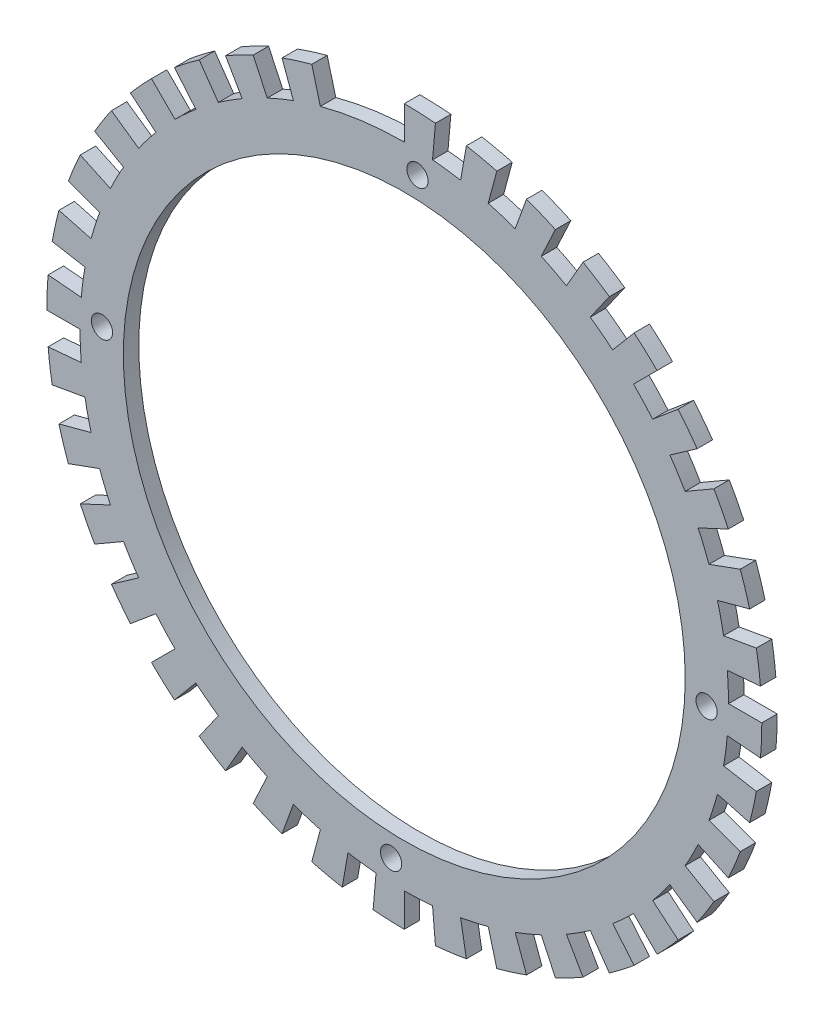
SolidWorks part; units mm, degrees
ref_plane "Front Plane" through (0, 0, 0) normal (0, 0, 1) x (1, 0, 0)
ref_plane "Top Plane" through (0, 0, 0) normal (0, 1, 0) x (1, 0, 0)
ref_plane "Right Plane" through (0, 0, 0) normal (1, 0, 0) x (0, 0, -1)
sketch "Sketch1" plane through (0, 0, 0) normal (0, 0, 1) x (1, 0, 0)
  line L0 (0, 82.7) -> (0, 75)
  line L1 (7.2078, 82.3853) -> (6.5367, 74.7146)
  line L2 (0, 75) -> (0, 0) construction
  line L3 (6.5367, 74.7146) -> (0, 0) construction
  line L4 (13.0236, 73.8606) -> (14.3607, 81.4436)
  line L5 (13.0236, 73.8606) -> (0, 0) construction
  line L6 (-0.3129, 74.9993) -> (0, 75)
  line L7 (21.4043, 79.8821) -> (19.4114, 72.4444)
  line L8 (0, 0) -> (3.0531, 69.9286) construction
  line L9 (28.2851, 77.7126) -> (25.6515, 70.4769)
  line L10 (34.9505, 74.9517) -> (31.6964, 67.9731)
  line L11 (37.5, 64.9519) -> (41.35, 71.6203)
  line L12 (3.2715, 74.9286) -> (3.0531, 69.9286) construction
  line L13 (47.4348, 67.7439) -> (43.0182, 61.4364)
  line L14 (48.2091, 57.4533) -> (53.1585, 63.3519)
  line L15 (3.0531, 69.9286) -> (2.8348, 64.9286) construction
  line L16 (58.4777, 58.4777) -> (53.033, 53.033)
  line L17 (57.4533, 48.2091) -> (63.3519, 53.1585)
  line L19 (67.7439, 47.4348) -> (61.4364, 43.0182)
  line L20 (64.9519, 37.5) -> (71.6203, 41.35)
  line L22 (74.9517, 34.9505) -> (67.9731, 31.6964)
  line L23 (70.4769, 25.6515) -> (77.7126, 28.2851)
  line L25 (79.8821, 21.4043) -> (72.4444, 19.4114)
  line L26 (73.8606, 13.0236) -> (81.4436, 14.3607)
  line L28 (82.3853, 7.2078) -> (74.7146, 6.5367)
  line L29 (75, 0) -> (82.7, 0)
  line L31 (82.3853, -7.2078) -> (74.7146, -6.5367)
  line L32 (73.8606, -13.0236) -> (81.4436, -14.3607)
  line L34 (79.8821, -21.4043) -> (72.4444, -19.4114)
  line L35 (70.4769, -25.6515) -> (77.7126, -28.2851)
  line L37 (74.9517, -34.9505) -> (67.9731, -31.6964)
  line L38 (64.9519, -37.5) -> (71.6203, -41.35)
  line L40 (67.7439, -47.4348) -> (61.4364, -43.0182)
  line L41 (57.4533, -48.2091) -> (63.3519, -53.1585)
  line L43 (58.4777, -58.4777) -> (53.033, -53.033)
  line L44 (48.2091, -57.4533) -> (53.1585, -63.3519)
  line L46 (47.4348, -67.7439) -> (43.0182, -61.4364)
  line L47 (37.5, -64.9519) -> (41.35, -71.6203)
  line L49 (34.9505, -74.9517) -> (31.6964, -67.9731)
  line L50 (25.6515, -70.4769) -> (28.2851, -77.7126)
  line L52 (21.4043, -79.8821) -> (19.4114, -72.4444)
  line L53 (13.0236, -73.8606) -> (14.3607, -81.4436)
  line L55 (7.2078, -82.3853) -> (6.5367, -74.7146)
  line L56 (0, -75) -> (0, -82.7)
  line L58 (-7.2078, -82.3853) -> (-6.5367, -74.7146)
  line L60 (-14.3607, -81.4436) -> (-13.0236, -73.8606)
  line L61 (-21.4043, -79.8821) -> (-19.4114, -72.4444)
  line L63 (-28.2851, -77.7126) -> (-25.6515, -70.4769)
  line L64 (-34.9505, -74.9517) -> (-31.6964, -67.9731)
  line L66 (-41.35, -71.6203) -> (-37.5, -64.9519)
  line L67 (-47.4348, -67.7439) -> (-43.0182, -61.4364)
  line L69 (-53.1585, -63.3519) -> (-48.2091, -57.4533)
  line L70 (-58.4777, -58.4777) -> (-53.033, -53.033)
  line L71 (-57.4533, -48.2091) -> (-63.3519, -53.1585)
  line L73 (-67.7439, -47.4348) -> (-61.4364, -43.0182)
  line L75 (-71.6203, -41.35) -> (-64.9519, -37.5)
  line L76 (-74.9517, -34.9505) -> (-67.9731, -31.6964)
  line L78 (-77.7126, -28.2851) -> (-70.4769, -25.6515)
  line L79 (-79.8821, -21.4043) -> (-72.4444, -19.4114)
  line L81 (-81.4436, -14.3607) -> (-73.8606, -13.0236)
  line L82 (-82.3853, -7.2078) -> (-74.7146, -6.5367)
  line L84 (-82.7, 0) -> (-75, 0)
  line L85 (-82.3853, 7.2078) -> (-74.7146, 6.5367)
  line L87 (-81.4436, 14.3607) -> (-73.8606, 13.0236)
  line L88 (-79.8821, 21.4043) -> (-72.4444, 19.4114)
  line L90 (-77.7126, 28.2851) -> (-70.4769, 25.6515)
  line L91 (-74.9517, 34.9505) -> (-67.9731, 31.6964)
  line L93 (-71.6203, 41.35) -> (-64.9519, 37.5)
  line L94 (-67.7439, 47.4348) -> (-61.4364, 43.0182)
  line L96 (-63.3519, 53.1585) -> (-57.4533, 48.2091)
  line L97 (-58.4777, 58.4777) -> (-53.033, 53.033)
  line L99 (-53.1585, 63.3519) -> (-48.2091, 57.4533)
  line L100 (-47.4348, 67.7439) -> (-43.0182, 61.4364)
  line L102 (-41.35, 71.6203) -> (-37.5, 64.9519)
  line L103 (-34.9505, 74.9517) -> (-31.6964, 67.9731)
  line L105 (-28.2851, 77.7126) -> (-25.6515, 70.4769)
  line L106 (-21.4043, 79.8821) -> (-19.4114, 72.4444)
  line L109 (0, -82.7) -> (0, -75) [skipped]
  line L111 (14.3607, 81.4436) -> (13.0236, 73.8606) [skipped]
  line L115 (41.35, 71.6203) -> (37.5, 64.9519) [skipped]
  line L117 (53.1585, 63.3519) -> (48.2091, 57.4533) [skipped]
  line L118 (-63.3519, -53.1585) -> (-57.4533, -48.2091) [skipped]
  line L119 (63.3519, 53.1585) -> (57.4533, 48.2091) [skipped]
  line L121 (71.6203, 41.35) -> (64.9519, 37.5) [skipped]
  line L123 (77.7126, 28.2851) -> (70.4769, 25.6515) [skipped]
  line L125 (81.4436, 14.3607) -> (73.8606, 13.0236) [skipped]
  line L127 (82.7, 0) -> (75, 0) [skipped]
  line L129 (81.4436, -14.3607) -> (73.8606, -13.0236) [skipped]
  line L131 (77.7126, -28.2851) -> (70.4769, -25.6515) [skipped]
  line L133 (71.6203, -41.35) -> (64.9519, -37.5) [skipped]
  line L135 (63.3519, -53.1585) -> (57.4533, -48.2091) [skipped]
  line L137 (53.1585, -63.3519) -> (48.2091, -57.4533) [skipped]
  line L139 (41.35, -71.6203) -> (37.5, -64.9519) [skipped]
  line L141 (28.2851, -77.7126) -> (25.6515, -70.4769) [skipped]
  line L142 (14.3607, -81.4436) -> (13.0236, -73.8606) [skipped]
  circle A0 centre (0, 0) radius 82.7 construction
  circle A1 centre (0, 0) radius 64.9905
  arc A2 (6.5367, 74.7146) -> (13.0236, 73.8606) centre (0, 0) cw
  arc A3 (0, 82.7) -> (7.2078, 82.3853) centre (0, 0) cw
  arc A4 (14.3607, 81.4436) -> (21.4043, 79.8821) centre (0, 0) cw
  arc A5 (19.4114, 72.4444) -> (25.6515, 70.4769) centre (0, 0) cw
  arc A6 (28.2851, 77.7126) -> (34.9505, 74.9517) centre (0, 0) cw
  arc A7 (31.6964, 67.9731) -> (37.5, 64.9519) centre (0, 0) cw
  arc A8 (41.35, 71.6203) -> (47.4348, 67.7439) centre (0, 0) cw
  arc A9 (43.0182, 61.4364) -> (48.2091, 57.4533) centre (0, 0) cw
  arc A10 (53.1585, 63.3519) -> (58.4777, 58.4777) centre (0, 0) cw
  arc A11 (53.033, 53.033) -> (57.4533, 48.2091) centre (0, 0) cw
  arc A12 (63.3519, 53.1585) -> (67.7439, 47.4348) centre (0, 0) cw
  arc A13 (61.4364, 43.0182) -> (64.9519, 37.5) centre (0, 0) cw
  arc A14 (71.6203, 41.35) -> (74.9517, 34.9505) centre (0, 0) cw
  arc A15 (67.9731, 31.6964) -> (70.4769, 25.6515) centre (0, 0) cw
  arc A16 (77.7126, 28.2851) -> (79.8821, 21.4043) centre (0, 0) cw
  arc A17 (72.4444, 19.4114) -> (73.8606, 13.0236) centre (0, 0) cw
  arc A18 (81.4436, 14.3607) -> (82.3853, 7.2078) centre (0, 0) cw
  arc A19 (74.7146, 6.5367) -> (75, 0) centre (0, 0) cw
  arc A20 (82.7, 0) -> (82.3853, -7.2078) centre (0, 0) cw
  arc A21 (74.7146, -6.5367) -> (73.8606, -13.0236) centre (0, 0) cw
  arc A22 (81.4436, -14.3607) -> (79.8821, -21.4043) centre (0, 0) cw
  arc A23 (72.4444, -19.4114) -> (70.4769, -25.6515) centre (0, 0) cw
  arc A24 (77.7126, -28.2851) -> (74.9517, -34.9505) centre (0, 0) cw
  arc A25 (67.9731, -31.6964) -> (64.9519, -37.5) centre (0, 0) cw
  arc A26 (71.6203, -41.35) -> (67.7439, -47.4348) centre (0, 0) cw
  arc A27 (61.4364, -43.0182) -> (57.4533, -48.2091) centre (0, 0) cw
  arc A28 (63.3519, -53.1585) -> (58.4777, -58.4777) centre (0, 0) cw
  arc A29 (53.033, -53.033) -> (48.2091, -57.4533) centre (0, 0) cw
  arc A30 (53.1585, -63.3519) -> (47.4348, -67.7439) centre (0, 0) cw
  arc A31 (43.0182, -61.4364) -> (37.5, -64.9519) centre (0, 0) cw
  arc A32 (41.35, -71.6203) -> (34.9505, -74.9517) centre (0, 0) cw
  arc A33 (31.6964, -67.9731) -> (25.6515, -70.4769) centre (0, 0) cw
  arc A34 (28.2851, -77.7126) -> (21.4043, -79.8821) centre (0, 0) cw
  arc A35 (19.4114, -72.4444) -> (13.0236, -73.8606) centre (0, 0) cw
  arc A36 (14.3607, -81.4436) -> (7.2078, -82.3853) centre (0, 0) cw
  arc A37 (6.5367, -74.7146) -> (0, -75) centre (0, 0) cw
  arc A38 (0, -82.7) -> (-7.2078, -82.3853) centre (0, 0) cw
  arc A39 (-6.5367, -74.7146) -> (-13.0236, -73.8606) centre (0, 0) cw
  arc A40 (-14.3607, -81.4436) -> (-21.4043, -79.8821) centre (0, 0) cw
  arc A41 (-19.4114, -72.4444) -> (-25.6515, -70.4769) centre (0, 0) cw
  arc A42 (-28.2851, -77.7126) -> (-34.9505, -74.9517) centre (0, 0) cw
  arc A43 (-31.6964, -67.9731) -> (-37.5, -64.9519) centre (0, 0) cw
  arc A44 (-41.35, -71.6203) -> (-47.4348, -67.7439) centre (0, 0) cw
  arc A45 (-43.0182, -61.4364) -> (-48.2091, -57.4533) centre (0, 0) cw
  arc A46 (-53.1585, -63.3519) -> (-58.4777, -58.4777) centre (0, 0) cw
  arc A47 (-53.033, -53.033) -> (-57.4533, -48.2091) centre (0, 0) cw
  arc A48 (-63.3519, -53.1585) -> (-67.7439, -47.4348) centre (0, 0) cw
  arc A49 (-61.4364, -43.0182) -> (-64.9519, -37.5) centre (0, 0) cw
  arc A50 (-71.6203, -41.35) -> (-74.9517, -34.9505) centre (0, 0) cw
  arc A51 (-67.9731, -31.6964) -> (-70.4769, -25.6515) centre (0, 0) cw
  arc A52 (-77.7126, -28.2851) -> (-79.8821, -21.4043) centre (0, 0) cw
  arc A53 (-72.4444, -19.4114) -> (-73.8606, -13.0236) centre (0, 0) cw
  arc A54 (-81.4436, -14.3607) -> (-82.3853, -7.2078) centre (0, 0) cw
  arc A55 (-74.7146, -6.5367) -> (-75, 0) centre (0, 0) cw
  arc A56 (-82.7, 0) -> (-82.3853, 7.2078) centre (0, 0) cw
  arc A57 (-74.7146, 6.5367) -> (-73.8606, 13.0236) centre (0, 0) cw
  arc A58 (-81.4436, 14.3607) -> (-79.8821, 21.4043) centre (0, 0) cw
  arc A59 (-72.4444, 19.4114) -> (-70.4769, 25.6515) centre (0, 0) cw
  arc A60 (-77.7126, 28.2851) -> (-74.9517, 34.9505) centre (0, 0) cw
  arc A61 (-67.9731, 31.6964) -> (-64.9519, 37.5) centre (0, 0) cw
  arc A62 (-71.6203, 41.35) -> (-67.7439, 47.4348) centre (0, 0) cw
  arc A63 (-61.4364, 43.0182) -> (-57.4533, 48.2091) centre (0, 0) cw
  arc A64 (-63.3519, 53.1585) -> (-58.4777, 58.4777) centre (0, 0) cw
  arc A65 (-53.033, 53.033) -> (-48.2091, 57.4533) centre (0, 0) cw
  arc A66 (-53.1585, 63.3519) -> (-47.4348, 67.7439) centre (0, 0) cw
  arc A67 (-43.0182, 61.4364) -> (-37.5, 64.9519) centre (0, 0) cw
  arc A68 (-41.35, 71.6203) -> (-34.9505, 74.9517) centre (0, 0) cw
  arc A69 (-31.6964, 67.9731) -> (-25.6515, 70.4769) centre (0, 0) cw
  arc A70 (-28.2851, 77.7126) -> (-21.4043, 79.8821) centre (0, 0) cw
  arc A71 (-19.4114, 72.4444) -> (-13.0236, 73.8606) centre (0, 0) cw
  arc A72 (-13.0236, 73.8606) -> (-0.3129, 74.9993) centre (0, 0) cw
  circle A73 centre (3.0531, 69.9286) radius 2.4585
  circle A74 centre (3.0531, 69.9286) radius 2.987 construction
  circle A75 centre (69.9286, -3.0531) radius 2.4585
  circle A76 centre (-3.0531, -69.9286) radius 2.4585
  circle A77 centre (-69.9286, 3.0531) radius 2.4585
  arc A78 (0, 75) -> (6.5367, 74.7146) centre (0, 0) cw construction
  point P34 (0, 0)
  point P252 (0, 0)
  dimension "D1" = 5
  dimension "D2" = 165.4
  dimension "D7" = 4.917
  dimension "D8" = 5.974
  dimension "D3" = 5
  dimension "D4" = 7.7
  dimension "D6" = 2.5
  dimension "D10" = 69.9952
  dimension "D5" = 35
  dimension "D9" = 4
extrude "Boss-Extrude1" add sketch "Sketch1" along normal blind 3.5719
